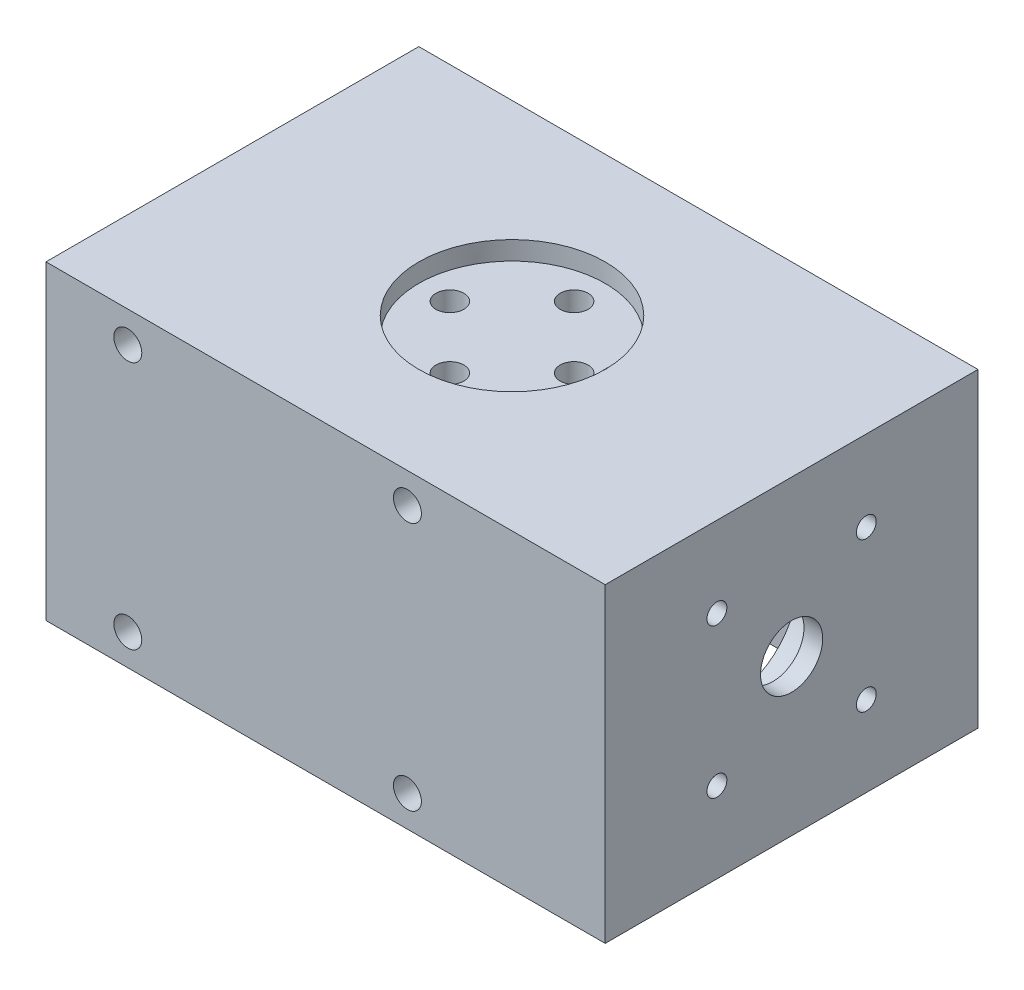
SolidWorks part; units mm, degrees
ref_plane "Front Plane" through (0, 0, 0) normal (0, 0, 1) x (1, 0, 0)
ref_plane "Top Plane" through (0, 0, 0) normal (0, 1, 0) x (1, 0, 0)
ref_plane "Right Plane" through (0, 0, 0) normal (1, 0, 0) x (0, 0, -1)
sketch "Sketch1" plane through (0, 0, 0) normal (0, 1, 0) x (1, 0, 0)
  line L6 (-45, 30) -> (45, 30)
  line L10 (-45, 30) -> (-45, -30)
  line L11 (-45, -30) -> (45, -30)
  line L12 (45, 30) -> (45, -30)
  line L13 (-45, 30) -> (45, -30) construction
  line L14 (-45, -30) -> (45, 30) construction
  circle A0 centre (0, 0) radius 15
  circle A1 centre (0, 0) radius 10 construction
  circle A2 centre (0, 10) radius 2.25
  circle A3 centre (10, 0) radius 2.25
  circle A4 centre (0, -10) radius 2.25
  circle A5 centre (-10, 0) radius 2.25
  point P15 (0, 0)
  dimension "D1" = 30
  dimension "D2" = 4
  dimension "D5" = 4.5
  dimension "D3" = 60
  dimension "D4" = 90
extrude "Boss-Extrude1" add sketch "Sketch1" along normal blind 50 contours A0 | A5 | A0 A5 A4 A3 A2 | A4 | A3 | A2 region at (0, 0, -28.9183) region at (0, 0, 0) region at (0, 0, -10) region at (10, 0, 0) region at (0, 0, 10) region at (-10, 0, 0)
sketch "Sketch2" plane through (0, 0, 0) normal (0, -1, 0) x (1, 0, 0)
  line L0 (-45, -30) -> (-45, 30) construction
  line L1 (-35, 25) -> (35, 25)
  line L2 (-35, 25) -> (-35, -25)
  line L3 (-35, -25) -> (35, -25)
  line L4 (35, 25) -> (35, -25)
  line L5 (-35, 25) -> (35, -25) construction
  line L6 (-35, -25) -> (35, 25) construction
  line L7 (-45, 30) -> (45, 30) construction
  point P0 (0, 0)
  point P6 (-35, 0)
  dimension "D1" = 10
  dimension "D2" = 5
extrude "Cut-Extrude1" cut sketch "Sketch2" against normal blind 40
extrude "Cut-Extrude3" cut sketch "Sketch1<5>" against normal blind 40 from surface contours A4 | A5 | A2 | A3 region at (0, 0, -10) region at (10, 0, 0) region at (0, 0, 10) region at (-10, 0, 0) starting at face at (0, 50, 0)
sketch "Sketch1<5>" plane through (0, 0, 0) normal (0, 1, 0) x (1, 0, 0) same geometry as "Sketch1"
extrude "Cut-Extrude4" cut sketch "Sketch1<6>" against normal blind 3 from surface contours A0 A5 A4 A3 A2 region at (0, 0, 0) starting at face at (0, 50, 12.25)
sketch "Sketch1<6>" plane through (0, 0, 0) normal (0, 1, 0) x (1, 0, 0) same geometry as "Sketch1"
sketch "Sketch3" plane through (-45, 0, 0) normal (-1, 0, 0) x (0, 0, 1)
  line L0 (-30, 50) -> (30, 50) construction
  line L1 (0, 50) -> (0, 0) construction
  line L2 (0, 25) -> (17, 25) construction
  line L3 (-15, 40) -> (15, 40) construction
  line L4 (-15, 40) -> (-15, 10) construction
  line L5 (-15, 10) -> (15, 10) construction
  line L6 (15, 40) -> (15, 10) construction
  line L7 (-15, 40) -> (15, 10) construction
  line L8 (-15, 10) -> (15, 40) construction
  circle A0 centre (0, 25) radius 5
  circle A1 centre (0, 25) radius 11
  circle A2 centre (0, 25) radius 17 construction
  circle A3 centre (-12.0208, 37.0208) radius 1.6
  circle A4 centre (12.0208, 37.0208) radius 1.6
  circle A5 centre (12.0208, 12.9792) radius 1.6
  circle A6 centre (-12.0208, 12.9792) radius 1.6
  point P0 (0, 50)
  point P1 (0, 0)
  point P7 (0, 25)
  dimension "D1" = 30
  dimension "D3" = 10
  dimension "D2" = 30
extrude "Cut-Extrude5" cut sketch "Sketch3" against normal through all contours A0 L1 | L1 A0 region at (-45, 25, 2.1221) region at (-45, 25, -2.1221)
extrude "Cut-Extrude7" cut sketch "Sketch3<3>" along normal blind 7 from surface starting at face at (-35, 25, 5)
sketch "Sketch3<3>" plane through (-45, 0, 0) normal (-1, 0, 0) x (0, 0, 1) same geometry as "Sketch3"
extrude "Cut-Extrude8" cut sketch "Sketch3<4>" against normal blind 7 from surface starting at face at (35, 25, -5)
sketch "Sketch3<4>" plane through (-45, 0, 0) normal (-1, 0, 0) x (0, 0, 1) same geometry as "Sketch3"
extrude "Cut-Extrude9" cut sketch "Sketch3<5>" against normal through all contours A3 | A4 | A5 | A6 region at (-45, 37.0208, -12.0208) region at (-45, 37.0208, 12.0208) region at (-45, 12.9792, 12.0208) region at (-45, 12.9792, -12.0208)
sketch "Sketch3<5>" plane through (-45, 0, 0) normal (-1, 0, 0) x (0, 0, 1) same geometry as "Sketch3"
sketch "Sketch4" plane through (0, 0, 30) normal (0, 0, 1) x (1, 0, 0)
  line L0 (13.1662, 5) -> (13.1662, 45.1039) construction
  line L1 (28.1662, 50) -> (-44.8338, 50) construction
  line L2 (28.1662, 50) -> (28.1662, 0) construction
  line L3 (28.1662, 0) -> (-44.8338, 0) construction
  line L4 (-44.8338, 50) -> (-44.8338, 0) construction
  line L6 (-45, 0) -> (45, 0) construction
  line L7 (-36.8338, 45) -> (-36.8338, 5) construction
  line L12 (-36.8338, 5) -> (23.1662, 5) construction
  line L13 (23.1718, 45.1247) -> (23.1662, 5) construction
  line L14 (-36.8338, 45) -> (23.1718, 45.1247) construction
  line L15 (-31.8338, 5) -> (-31.8338, 45.0104) construction
  circle A4 centre (-31.8338, 5) radius 2.25
  circle A5 centre (-31.8338, 45.0104) radius 2.25
  circle A6 centre (13.1662, 5) radius 2.25
  circle A7 centre (13.1662, 45.1039) radius 2.25
  point P4 (13.1662, 5)
  point P7 (-41.8338, 50)
  point P16 (-31.8338, 5)
  dimension "D3" = 5
  dimension "D4" = 10
  dimension "D1" = 73
  dimension "D2" = 3
extrude "Cut-Extrude10" cut sketch "Sketch4" against normal blind 60
